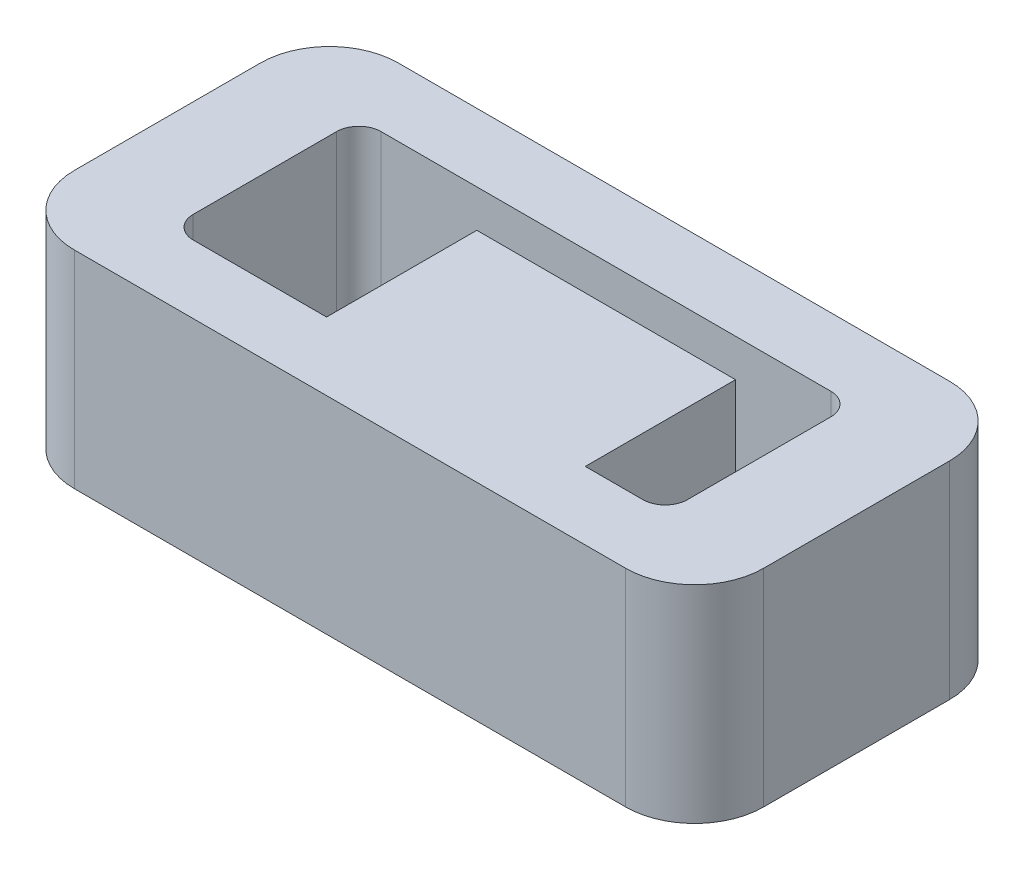
SolidWorks part; units mm, degrees
material "K110"
ref_plane "Front Plane" through (0, 0, 0) normal (0, 0, 1) x (1, 0, 0)
ref_plane "Top Plane" through (0, 0, 0) normal (0, 1, 0) x (1, 0, 0)
ref_plane "Right Plane" through (0, 0, 0) normal (1, 0, 0) x (0, 0, -1)
sketch "Sketch2" plane through (0, 0, 0) normal (0, 1, 0) x (1, 0, 0)
  line L1 (-50, -23.5) -> (50, -23.5)
  line L2 (-50, -23.5) -> (-50, 23.5)
  line L3 (-50, 23.5) -> (50, 23.5)
  line L4 (50, -23.5) -> (50, 23.5)
  line L5 (-50, -23.5) -> (50, 23.5) construction
  line L6 (-50, 23.5) -> (50, -23.5) construction
  point P0 (0, 0)
  dimension "D1" = 100
  dimension "D2" = 47
extrude "Boss-Extrude1" add sketch "Sketch2" against normal blind 30
fillet "Fillet1" radius 10 4 edges at (-50, -15, -23.5) (50, -15, -23.5) (50, -15, 23.5) (-50, -15, 23.5)
sketch "Sketch3" plane through (0, 0, 0) normal (0, 1, 0) x (1, 0, 0)
  line L16 (35.855, -10.4) -> (35.855, 10.4)
  line L17 (24.265, -13.63) -> (32.625, -13.63)
  line L18 (24.265, 8.17) -> (24.265, -13.63)
  line L19 (-13.275, 8.17) -> (24.265, 8.17)
  line L20 (-13.275, -13.63) -> (-13.275, 8.17)
  line L21 (-32.625, -13.63) -> (-13.275, -13.63)
  line L22 (-35.855, 10.4) -> (-35.855, -10.4)
  line L23 (32.625, 13.63) -> (-32.625, 13.63)
  line L24 (35.855, -10.4) -> (35.855, 10.4)
  line L25 (24.265, -13.63) -> (32.625, -13.63)
  line L26 (24.265, 8.17) -> (24.265, -13.63)
  line L27 (-13.275, 8.17) -> (24.265, 8.17)
  line L28 (-13.275, -13.63) -> (-13.275, 8.17)
  line L29 (-32.625, -13.63) -> (-13.275, -13.63)
  line L30 (-35.855, 10.4) -> (-35.855, -10.4)
  line L31 (32.625, 13.63) -> (-32.625, 13.63)
  arc A8 (35.855, 10.4) -> (32.625, 13.63) centre (32.625, 10.4) ccw
  arc A9 (32.625, -13.63) -> (35.855, -10.4) centre (32.625, -10.4) ccw
  arc A10 (-35.855, -10.4) -> (-32.625, -13.63) centre (-32.625, -10.4) ccw
  arc A11 (-32.625, 13.63) -> (-35.855, 10.4) centre (-32.625, 10.4) ccw
  arc A12 (35.855, 10.4) -> (32.625, 13.63) centre (32.625, 10.4) ccw
  arc A13 (32.625, -13.63) -> (35.855, -10.4) centre (32.625, -10.4) ccw
  arc A14 (-35.855, -10.4) -> (-32.625, -13.63) centre (-32.625, -10.4) ccw
  arc A15 (-32.625, 13.63) -> (-35.855, 10.4) centre (-32.625, 10.4) ccw
  dimension "D1" = 0.23
extrude "Cut-Extrude1" cut sketch "Sketch3" against normal up to next
hole_wizard "M6 Tapped Hole1" positions "Sketch6" profile "Sketch5" tap size "M6" standard "ISO"
sketch "Sketch6" plane through (0, -30, 0) normal (0, -1, 0) x (-1, 0, 0)
  line L0 (-50, -13.5) -> (-50, 13.5) construction
  line L1 (-40, 23.5) -> (40, 23.5) construction
  line L2 (40, -23.5) -> (-40, -23.5) construction
  line L3 (50, 13.5) -> (50, -13.5) construction
  point P0 (-43, 16.5)
  point P2 (43, 16.5)
  point P4 (43, -16.5)
  point P6 (-43, -16.5)
  dimension "D1" = 7
  dimension "D2" = 7
  dimension "D3" = 7
  dimension "D4" = 7
sketch "Sketch5" plane through (43, -30, -16.5) normal (1, 0, 0) x (0, 0, -1)
  line L0 (0, 0) -> (0, 18.5022)
  line L1 (0, 18.5022) -> (2.5, 17)
  line L2 (2.5, 17) -> (2.5, 0.525)
  line L3 (2.5, 0.525) -> (3.025, 0)
  line L5 (3.025, 0) -> (0, 0)
  line L6 (-2.5, 0.525) -> (-3.025, 0) construction
  line L10 (0, 18.5022) -> (-2.5, 17) construction
  line L11 (0, -6.35) -> (0, 107.95) construction
  dimension "Tap Drill Dia." = 5
  dimension "Tap Drill Depth" = 17
  dimension "Near C'Sink Dia." = 6.05
  dimension "Near C'Sink Angle" = 90
  dimension "Drill Angle" = 118
cosmetic thread "Hole Thread1"
cosmetic thread "Hole Thread2"
cosmetic thread "Hole Thread3"
cosmetic thread "Hole Thread4"
